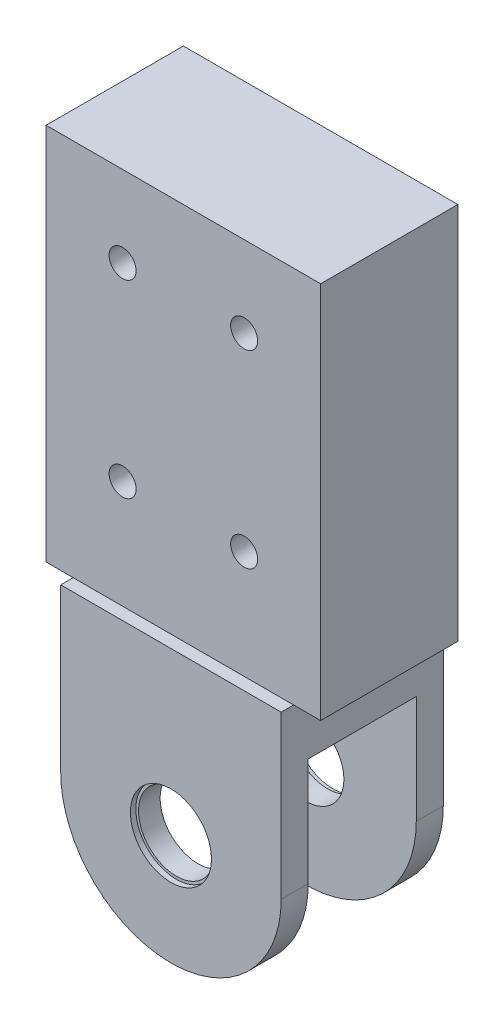
SolidWorks part; units mm, degrees
ref_plane "Front Plane" through (0, 0, 0) normal (0, 0, 1) x (1, 0, 0)
ref_plane "Top Plane" through (0, 0, 0) normal (0, 1, 0) x (1, 0, 0)
ref_plane "Right Plane" through (0, 0, 0) normal (1, 0, 0) x (0, 0, -1)
sketch "Sketch1" plane through (0, 0, 0) normal (0, 0, 1) x (1, 0, 0)
  line L0 (-25.4, 0) -> (-25.4, 100)
  line L1 (-25.4, 100) -> (25.4, 100)
  line L2 (25.4, 100) -> (25.4, 0)
  line L4 (-11.25, 85) -> (11.25, 85) construction
  line L5 (-11.25, 85) -> (-11.25, 50) construction
  line L6 (-11.25, 50) -> (11.25, 50) construction
  line L7 (11.25, 85) -> (11.25, 50) construction
  circle A0 centre (0, 0) radius 7
  arc A1 (-25.4, 0) -> (25.4, 0) centre (0, 0) ccw
  circle A2 centre (-11.25, 85) radius 2.5
  circle A3 centre (11.25, 85) radius 2.5
  circle A4 centre (11.25, 50) radius 2.5
  circle A5 centre (-11.25, 50) radius 2.5
  point P13 (0, 50)
  dimension "D1" = 14
  dimension "D4" = 5
  dimension "D2" = 50.8
  dimension "D3" = 100
  dimension "D5" = 35
  dimension "D6" = 15
  dimension "D7" = 22.5
extrude "Boss-Extrude1" add sketch "Sketch1" along normal blind 30
sketch "Sketch2" plane through (25.4, 0, 0) normal (1, 0, 0) x (0, 0, -1)
  line L0 (-30, -25.4) -> (0, -25.4) construction
  line L1 (-25, 20) -> (-5, 20)
  line L2 (-25, 20) -> (-25, -25.4)
  line L3 (-25, -25.4) -> (-5, -25.4)
  line L4 (-5, 20) -> (-5, -25.4)
  line L5 (-30, 0) -> (0, 0) construction
  point P8 (-15, 0)
  point P9 (-15, 20)
  dimension "D1" = 20
  dimension "D2" = 20
extrude "Cut-Extrude1" cut sketch "Sketch2" against normal through all
sketch "Sketch3" plane through (0, 0, 30) normal (0, 0, 1) x (1, 0, 0)
  circle A0 centre (0, 0) radius 7.5
  dimension "D1" = 15
extrude "Cut-Extrude2" cut sketch "Sketch3" against normal blind 1
sketch "Sketch4" plane through (0, 0, 0) normal (0, 0, -1) x (-1, 0, 0)
  circle A0 centre (0, 0) radius 7.5
  dimension "D1" = 15
extrude "Cut-Extrude3" cut sketch "Sketch4" against normal blind 1
sketch "Sketch5" plane through (25.4, 0, 0) normal (1, 0, 0) x (0, 0, -1)
  line L1 (-30, 100) -> (-27.7, 100)
  line L2 (-30, 100) -> (-30, 30)
  line L3 (-30, 30) -> (-27.7, 30)
  line L4 (-27.7, 100) -> (-27.7, 30)
  line L5 (0, 100) -> (-2.3, 100)
  line L6 (0, 100) -> (0, 30)
  line L7 (0, 30) -> (-2.3, 30)
  line L8 (-2.3, 100) -> (-2.3, 30)
  dimension "D1" = 70
  dimension "D2" = 25.4
extrude "Cut-Extrude4" cut sketch "Sketch5" against normal through all
sketch "Sketch6" plane through (0, 0, 30) normal (0, 0, 1) x (1, 0, 0)
  line L0 (-20.4, 0) -> (-20.4, 30)
  line L1 (-25.4, 30) -> (25.4, 30) construction
  line L3 (-25.4, 30) -> (25.4, 30) construction
  line L4 (20.4, 30) -> (20.4, 0)
  line L5 (-20.4, 30) -> (-25.4, 30)
  line L6 (-25.4, 30) -> (-25.4, -25.4)
  line L7 (-25.4, -25.4) -> (25.4, -25.4)
  line L8 (25.4, -25.4) -> (25.4, 30)
  line L9 (25.4, 30) -> (20.4, 30)
  arc A0 (-20.4, 0) -> (20.4, 0) centre (0, 0) ccw
  arc A1 (-25.4, 0) -> (25.4, 0) centre (0, 0) ccw construction
  point P19 (0, -25.4)
  dimension "D1" = 5
extrude "Cut-Extrude5" cut sketch "Sketch6" against normal through all
